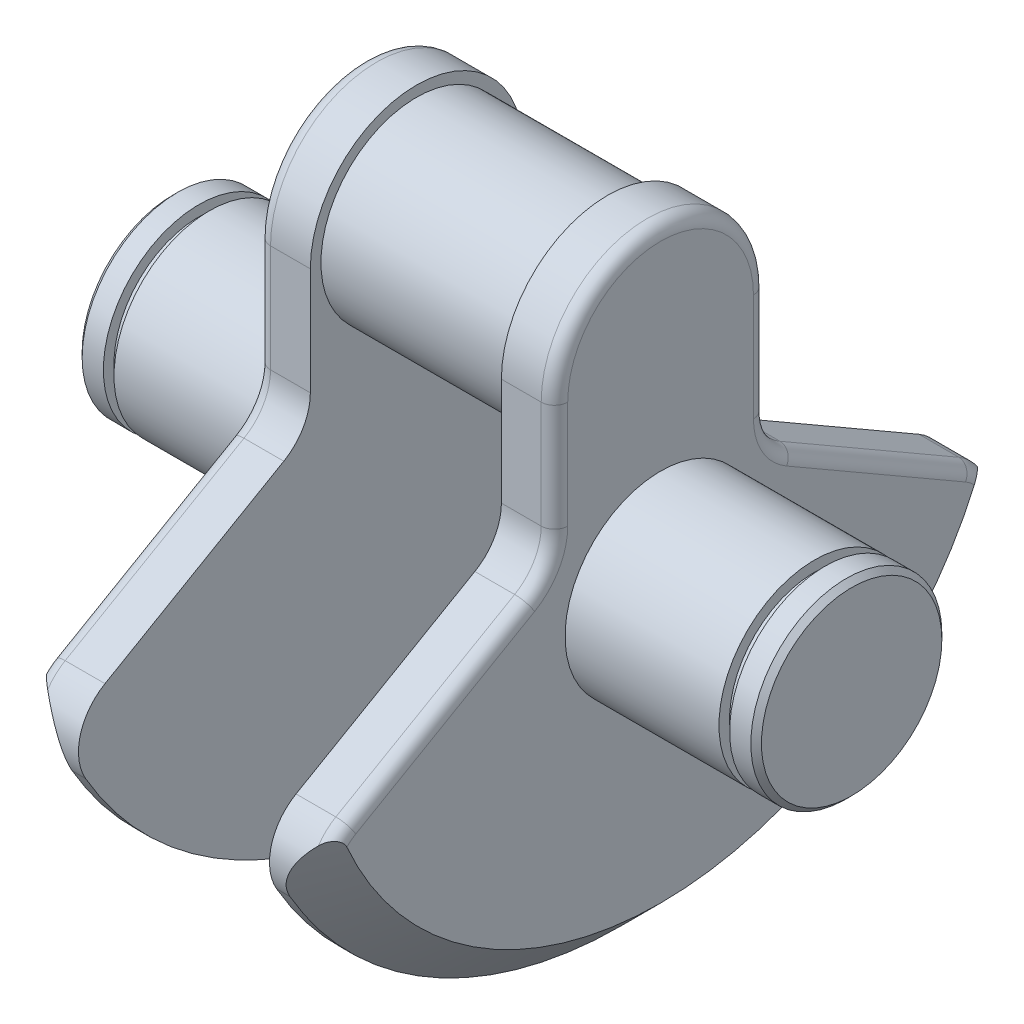
SolidWorks part; units mm, degrees
ref_plane "Front Plane" through (0, 0, 0) normal (0, 0, 1) x (1, 0, 0)
ref_plane "Top Plane" through (0, 0, 0) normal (0, 1, 0) x (1, 0, 0)
ref_plane "Right Plane" through (0, 0, 0) normal (1, 0, 0) x (0, 0, -1)
ref_plane "Plane1" through (18, 0, 0) normal (1, 0, 0) x (0, 0, -1)
ref_plane "Plane2" through (-18, 0, 0) normal (1, 0, 0) x (0, 0, -1)
sketch "Sketch1" plane through (18, 0, 0) normal (1, 0, 0) x (0, 0, -1)
  line L0 (0, 0) -> (0, -26) construction
  line L1 (-20, -26) -> (-59.4154, -48.7565) construction
  line L2 (20, -26) -> (59.4154, -48.7565) construction
  line L3 (-25, -28.8868) -> (-58.6936, -48.3397)
  line L4 (25, -28.8868) -> (58.6936, -48.3397)
  line L5 (-20, 0) -> (-20, -20.2265)
  line L6 (20, 0) -> (20, -20.2265)
  arc A0 (20, 0) -> (-20, 0) centre (0, 0) ccw
  arc A1 (-62.3538, -62) -> (62.3538, -62) centre (0, -26) ccw
  arc A2 (-58.6936, -48.3397) -> (-62.3538, -62) centre (-53.6936, -57) ccw
  arc A3 (58.6936, -48.3397) -> (62.3538, -62) centre (53.6936, -57) cw
  arc A4 (20, -20.2265) -> (25, -28.8868) centre (30, -20.2265) ccw
  arc A5 (-20, -20.2265) -> (-25, -28.8868) centre (-30, -20.2265) cw
  point P3 (0, 0)
  point P14 (-66.7495, -52.9908)
  point P17 (66.7495, -52.9908)
  dimension "D2" = 20
  dimension "D4" = 72
  dimension "D5" = 10
  dimension "D1" = 120
  dimension "D3" = 26
extrude "Boss-Extrude1" add sketch "Sketch1" along normal blind 10
chamfer "Chamfer1" distance 7.5 angle 45 1 edges at (28, -98, 0) tangent propagation no
fillet "Fillet1" radius 2.5 9 edges at (28, -48.8107, -59.4324) (28, -38.6132, -41.8468) (28, -25.2265, -21.3397) (28, -10.1132, -20) (28, -48.8107, 59.4324) (28, -38.6132, 41.8468) (28, -25.2265, 21.3397) (28, -10.1132, 20) (28, 20, 0)
sketch "Sketch2" plane through (-18, 0, 0) normal (1, 0, 0) x (0, 0, -1)
  line L4 (20, -20.2265) -> (20, 0)
  line L5 (58.6936, -48.3397) -> (25, -28.8868)
  line L6 (-25, -28.8868) -> (-58.6936, -48.3397)
  line L7 (-20, 0) -> (-20, -20.2265)
  line L8 (20, -20.2265) -> (20, 0)
  line L9 (58.6936, -48.3397) -> (25, -28.8868)
  line L10 (-25, -28.8868) -> (-58.6936, -48.3397)
  line L11 (-20, 0) -> (-20, -20.2265)
  arc A6 (20, 0) -> (-20, 0) centre (0, 0) ccw
  arc A7 (20, -20.2265) -> (25, -28.8868) centre (30, -20.2265) ccw
  arc A8 (62.3538, -62) -> (58.6936, -48.3397) centre (53.6936, -57) ccw
  arc A9 (-62.3538, -62) -> (62.3538, -62) centre (0, -26) ccw
  arc A10 (-58.6936, -48.3397) -> (-62.3538, -62) centre (-53.6936, -57) ccw
  arc A11 (-25, -28.8868) -> (-20, -20.2265) centre (-30, -20.2265) ccw
  arc A12 (20, 0) -> (-20, 0) centre (0, 0) ccw
  arc A13 (20, -20.2265) -> (25, -28.8868) centre (30, -20.2265) ccw
  arc A14 (62.3538, -62) -> (58.6936, -48.3397) centre (53.6936, -57) ccw
  arc A15 (-62.3538, -62) -> (62.3538, -62) centre (0, -26) ccw
  arc A16 (-58.6936, -48.3397) -> (-62.3538, -62) centre (-53.6936, -57) ccw
  arc A17 (-25, -28.8868) -> (-20, -20.2265) centre (-30, -20.2265) ccw
  dimension "D1" = 0
extrude "Boss-Extrude2" add sketch "Sketch2" against normal blind 10 separate body
chamfer "Chamfer2" distance 7.5 angle 45 1 edges at (-28, -98, 0) tangent propagation no
fillet "Fillet2" radius 2.5 9 edges at (-28, -48.8107, -59.4324) (-28, -38.6132, -41.8468) (-28, -25.2265, -21.3397) (-28, -10.1132, -20) (-28, -48.8107, 59.4324) (-28, -38.6132, 41.8468) (-28, -25.2265, 21.3397) (-28, -10.1132, 20) (-28, 20, 0)
sketch "Sketch3" plane through (0, 0, 0) normal (1, 0, 0) x (0, 0, -1)
  circle A0 centre (0, 0) radius 18
  dimension "D1" = 36
extrude "Boss-Extrude3" add sketch "Sketch3" along normal mid plane 36
sketch "Sketch4" plane through (28, 0, 0) normal (1, 0, 0) x (0, 0, -1)
  circle A0 centre (0, -38) radius 18
  point P2 (0, 0)
  dimension "D1" = 36
  dimension "D2" = 38
extrude "Boss-Extrude4" add sketch "Sketch4" along normal blind 36
sketch "Sketch5" plane through (0, 0, 0) normal (0, 0, 1) x (1, 0, 0)
  line L0 (64, -20) -> (28, -20) construction
  line L1 (57, -20) -> (59, -20)
  line L2 (57, -20) -> (57, -22)
  line L3 (57, -22) -> (59, -22)
  line L4 (59, -20) -> (59, -22)
  line L5 (64, -56) -> (64, -20) construction
  dimension "D1" = 2
  dimension "D2" = 2
  dimension "D3" = 5
revolve "Cut-Revolve1" cut sketch "Sketch5" angle 360 about axis through (64, -38, 0) along (-1, 0, 0)
chamfer "Chamfer3" distance 1 angle 45 1 edges at (64, -38, -18)
mirror "Mirror1" about plane through (0, 0, 0) normal (1, 0, 0) of "Chamfer3", "Cut-Revolve1", "Boss-Extrude4"
